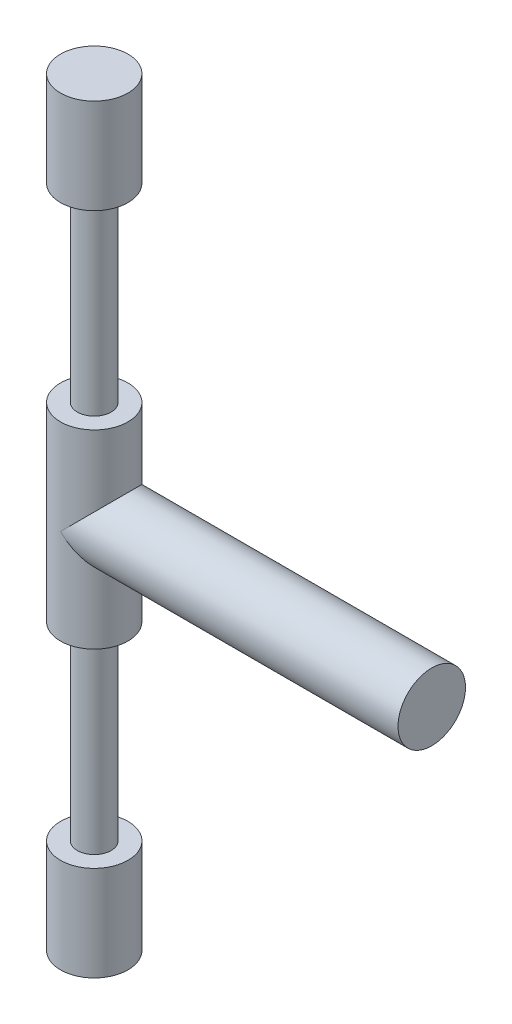
SolidWorks part; units mm, degrees
ref_plane "Front Plane" through (0, 0, 0) normal (0, 0, 1) x (1, 0, 0)
ref_plane "Top Plane" through (0, 0, 0) normal (0, 1, 0) x (1, 0, 0)
ref_plane "Right Plane" through (0, 0, 0) normal (1, 0, 0) x (0, 0, -1)
sketch "Sketch3" plane through (0, 0, 0) normal (1, 0, 0) x (0, 0, -1)
  circle A0 centre (0, 0) radius 1
  dimension "D1" = 2
extrude "Boss-Extrude1" add sketch "Sketch3" against normal blind 10
sketch "Sketch4" plane through (0, 0, 0) normal (0, 1, 0) x (1, 0, 0)
  line L0 (-10, 1) -> (-10, -1) construction
  line L1 (-10, 1) -> (-10, -1)
  circle A0 centre (-10, 0) radius 0.5
  dimension "D1" = 1
extrude "Boss-Extrude2" add sketch "Sketch4" along normal blind 11.25 and the other way blind 11.25 contours L1 A0 | L1 A0 region at (-9.7878, 0, 0) region at (-10.2122, 0, 0)
sketch "Sketch6" plane through (0, 0, 0) normal (0, 1, 0) x (1, 0, 0)
  circle A0 centre (-10, 0) radius 1
extrude "Boss-Extrude3" add sketch "Sketch6" along normal blind 2.8125 and the other way blind 2.8125 contours A0
sketch "Sketch7" plane through (0, 11.25, 0) normal (0, 1, 0) x (1, 0, 0)
  circle A0 centre (-10, 0) radius 1
  dimension "D1" = 2
extrude "Boss-Extrude4" add sketch "Sketch7" against normal blind 2.8125
mirror "Mirror1" about plane through (0, 0, 0) normal (0, 1, 0) of "Boss-Extrude4"
